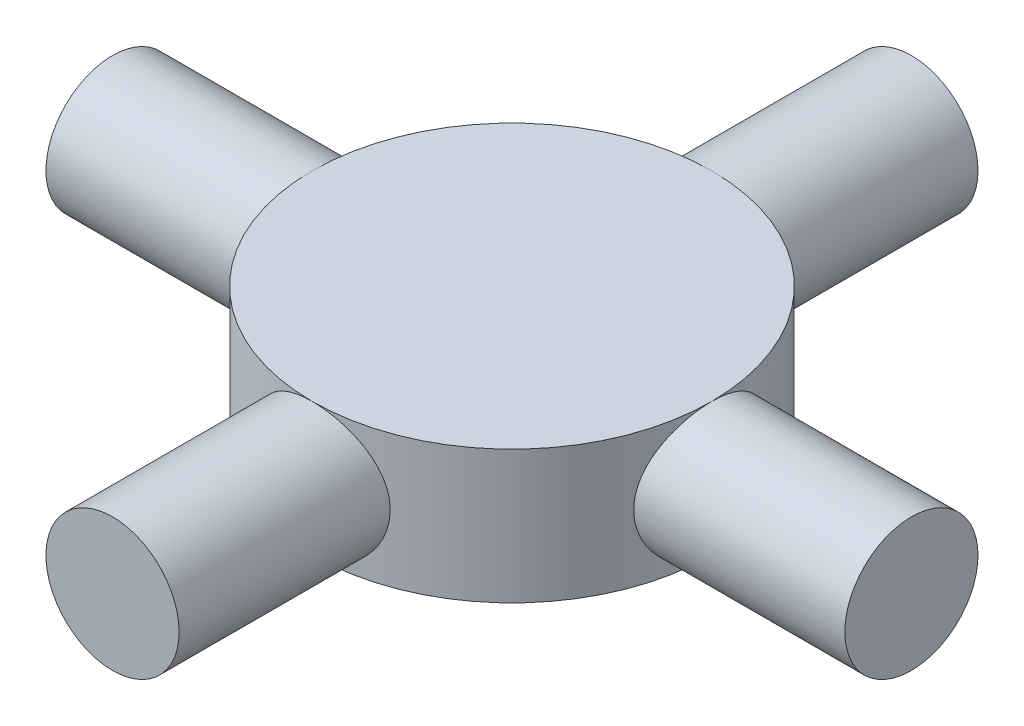
SolidWorks part; units mm, degrees
ref_plane "Front Plane" through (0, 0, 0) normal (0, 0, 1) x (1, 0, 0)
ref_plane "Top Plane" through (0, 0, 0) normal (0, 1, 0) x (1, 0, 0)
ref_plane "Right Plane" through (0, 0, 0) normal (1, 0, 0) x (0, 0, -1)
sketch "North-South Sketch" plane through (0, 0, 0) normal (0, 0, 1) x (1, 0, 0)
  circle A0 centre (0, 0) radius 5
  dimension "D1" = 10
extrude "North-South Extrude" add sketch "North-South Sketch" along normal blind 60
sketch "East-West Sketch" plane through (0, 0, 0) normal (1, 0, 0) x (0, 0, -1)
  line L0 (0, 5) -> (-60, 5) construction
  circle A0 centre (-30, 0) radius 5
  point P5 (-30, 5)
  dimension "D1" = 10
extrude "East-West Extrude" add sketch "East-West Sketch" along normal blind 30 and the other way blind 30
sketch "Center Support Sketch" plane through (0, 0, 0) normal (0, 1, 0) x (1, 0, 0)
  circle A0 centre (0, -30) radius 15
  dimension "D1" = 30
extrude "Center Support Extrude" add sketch "Center Support Sketch" along normal blind 5 and the other way blind 5
ref_plane "Mid Plane" through (0, 0, 30) normal (0, 0, -1) x (-1, 0, 0)
